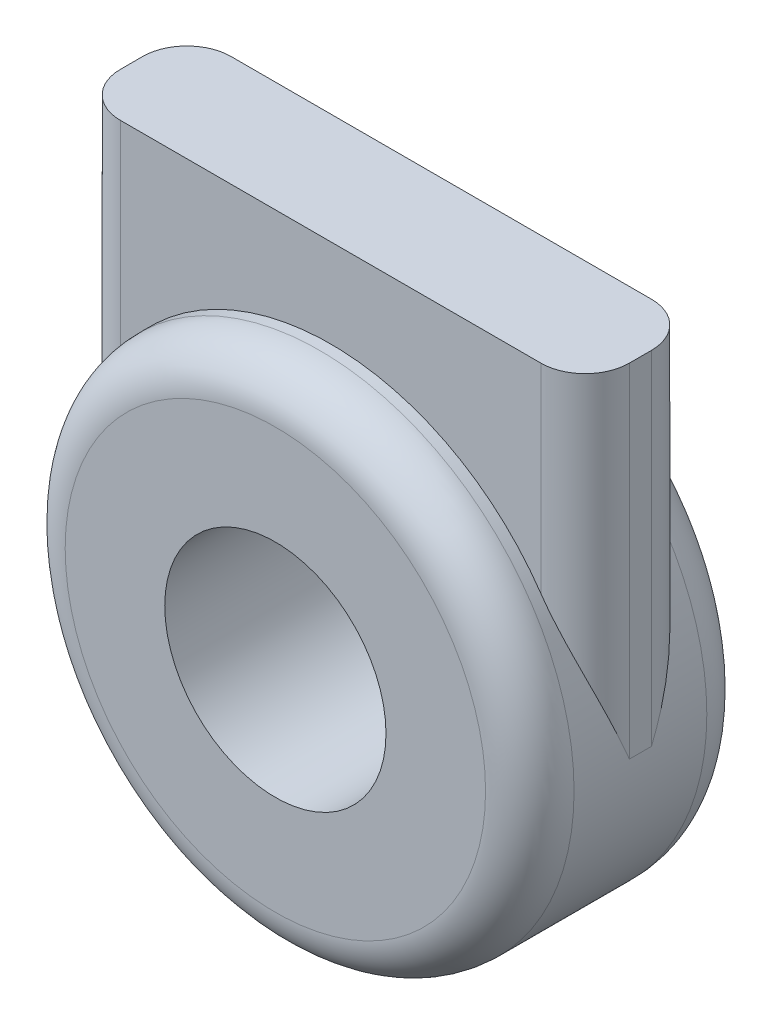
SolidWorks part; units mm, degrees
ref_plane "Front Plane" through (0, 0, 0) normal (0, 0, 1) x (1, 0, 0)
ref_plane "Top Plane" through (0, 0, 0) normal (0, 1, 0) x (1, 0, 0)
ref_plane "Right Plane" through (0, 0, 0) normal (1, 0, 0) x (0, 0, -1)
sketch "Sketch1" plane through (0, 0, 0) normal (0, 0, 1) x (1, 0, 0)
  line L0 (-11.5, 0) -> (-11.5, 11.5)
  line L1 (-11.5, 11.5) -> (-11.5, 15.5)
  line L2 (-11.5, 11.5) -> (11.5, 11.5)
  line L3 (11.5, 11.5) -> (11.5, 0)
  line L4 (-11.5, 15.5) -> (11.5, 15.5)
  line L5 (11.5, 15.5) -> (11.5, 11.5)
  circle A0 centre (0, 0) radius 5
  circle A1 centre (0, 0) radius 11.5
extrude "Boss-Extrude2" add sketch "Sketch1" along normal blind 5 contours A1 A0 | A1 L3 L2 | L5 L4 L1 L2 | A1 L2 L0 region at (-7.9017, 7.9017, 0) region at (-8.9313, 8.9313, 0) region at (0, 13.5, 0) region at (8.9313, 8.9313, 0)
sketch "Sketch3" plane through (0, 0, 5) normal (0, 0, 1) x (1, 0, 0)
  circle A0 centre (0, 0) radius 11.5
extrude "Boss-Extrude3" add sketch "Sketch3" along normal blind 2.5
sketch "Sketch4" plane through (0, 0, 0) normal (0, 0, -1) x (-1, 0, 0)
  circle A0 centre (0, 0) radius 11.5
extrude "Boss-Extrude4" add sketch "Sketch4" along normal blind 2.5
sketch "Sketch5" plane through (0, 0, 7.5) normal (0, 0, 1) x (1, 0, 0)
  circle A0 centre (0, 0) radius 5
extrude "Cut-Extrude2" cut sketch "Sketch5" against normal blind 17.5
fillet "Fillet1" radius 2 6 edges at (11.5, 0, 7.5) (-11.5, 0, -2.5)
